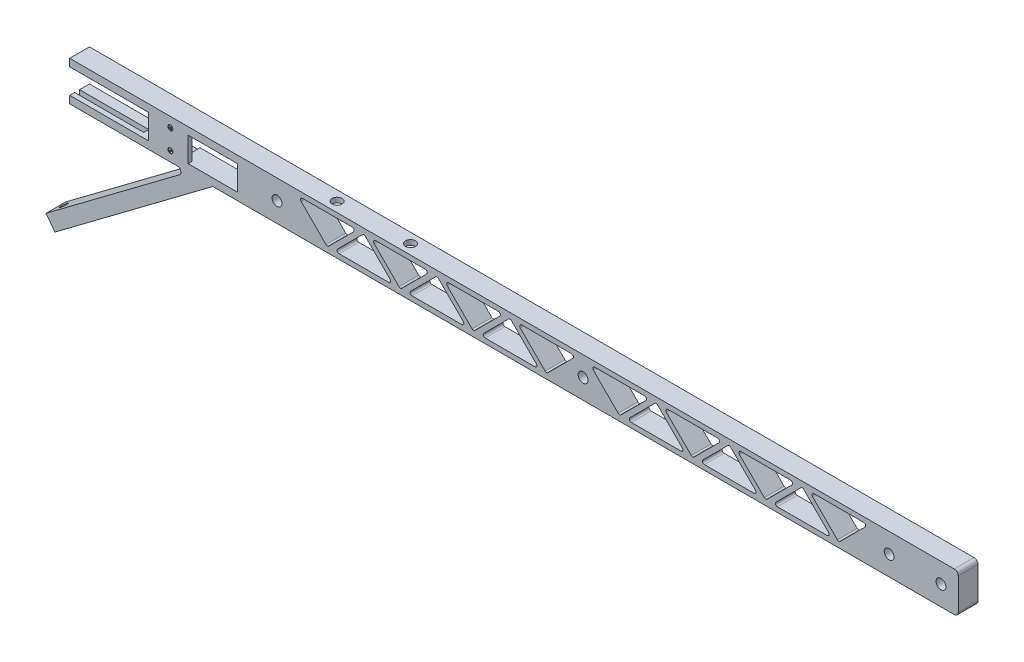
SolidWorks part; units mm, degrees
ref_plane "Front Plane" through (0, 0, 0) normal (0, 0, 1) x (1, 0, 0)
ref_plane "Top Plane" through (0, 0, 0) normal (0, 1, 0) x (1, 0, 0)
ref_plane "Right Plane" through (0, 0, 0) normal (1, 0, 0) x (0, 0, -1)
sketch "Sketch1" plane through (0, 0, 0) normal (0, 0, 1) x (1, 0, 0)
  line L0 (2.54, 0) -> (568.96, 0)
  line L1 (571.5, 2.54) -> (571.5, 22.86)
  line L2 (568.96, 25.4) -> (2.54, 25.4)
  line L3 (0, 22.86) -> (0, 2.54)
  line L4 (0, 22.86) -> (0, 25.4)
  line L5 (0, 25.4) -> (2.54, 25.4)
  line L6 (0, 2.54) -> (0, 0)
  line L7 (0, 0) -> (2.54, 0)
  arc A1 (568.96, 25.4) -> (571.5, 22.86) centre (568.96, 22.86) cw
  arc A2 (571.5, 2.54) -> (568.96, 0) centre (568.96, 2.54) cw
  point P7 (0, 25.4)
  point P12 (571.5, 0)
  point P15 (0, 0)
  dimension "D3" = 2.54
  dimension "D1" = 571.5
  dimension "D2" = 25.4
extrude "Boss-Extrude1" add sketch "Sketch1" along normal blind 12.7
sketch "Sketch2" plane through (0, 0, 0) normal (0, 0, 1) x (1, 0, 0)
  line L0 (173.2461, 3.175) -> (205.2139, 3.175)
  line L1 (206.112, 5.343) -> (190.128, 21.327)
  line L2 (188.332, 21.327) -> (172.348, 5.343)
  line L3 (0, 0) -> (568.96, 0) construction
  line L4 (0, 25.4) -> (0, 0) construction
  arc A0 (188.332, 21.327) -> (190.128, 21.327) centre (189.23, 20.4289) cw
  arc A1 (206.112, 5.343) -> (205.2139, 3.175) centre (205.2139, 4.445) cw
  arc A2 (173.2461, 3.175) -> (172.348, 5.343) centre (173.2461, 4.445) cw
  point P9 (189.23, 22.225)
  point P12 (208.28, 3.175)
  point P15 (170.18, 3.175)
  dimension "D5" = 1.27
  dimension "D1" = 38.1
  dimension "D2" = 19.05
  dimension "D3" = 3.175
  dimension "D4" = 170.18
extrude "Cut-Extrude1" cut sketch "Sketch2" along normal blind 12.7
pattern_linear "LPattern1" count 7 spacing 46.99 along (1, 0, 0) skipping (3, 0) of "Cut-Extrude1"
sketch "Sketch3" plane through (0, 0, 0) normal (0, 0, 1) x (1, 0, 0)
  line L0 (149.7511, 22.225) -> (181.7189, 22.225)
  line L1 (182.617, 20.057) -> (166.633, 4.073)
  line L2 (164.837, 4.073) -> (148.853, 20.057)
  line L3 (568.96, 25.4) -> (0, 25.4) construction
  line L4 (0, 25.4) -> (0, 0) construction
  arc A0 (164.837, 4.073) -> (166.633, 4.073) centre (165.735, 4.9711) ccw
  arc A1 (182.617, 20.057) -> (181.7189, 22.225) centre (181.7189, 20.955) ccw
  arc A2 (149.7511, 22.225) -> (148.853, 20.057) centre (149.7511, 20.955) ccw
  point P9 (165.735, 3.175)
  point P12 (184.785, 22.225)
  point P15 (146.685, 22.225)
  dimension "D5" = 1.27
  dimension "D1" = 38.1
  dimension "D2" = 19.05
  dimension "D3" = 3.175
  dimension "D4" = 146.685
extrude "Cut-Extrude2" cut sketch "Sketch3" along normal blind 12.7
pattern_linear "LPattern2" count 8 spacing 46.99 along (1, 0, 0) of "Cut-Extrude2"
ref_plane "Plane1" through (292.1, 0, 0) normal (1, 0, 0) x (0, 0, -1)
sketch "Sketch8" plane through (0, 0, 0) normal (0, 0, 1) x (1, 0, 0)
  line L0 (92.075, 0) -> (-9.525, -76.2)
  line L1 (0, 0) -> (568.96, 0) construction
  line L2 (-9.525, -76.2) -> (-15.24, -68.58)
  line L3 (-15.24, -68.58) -> (76.2, 0)
  line L4 (76.2, 0) -> (92.075, 0)
  line L5 (0, 25.4) -> (0, 0) construction
  dimension "D1" = 76.2
  dimension "D2" = 101.6
  dimension "D3" = 9.525
  dimension "D4" = 76.2
extrude "Boss-Extrude3" add sketch "Sketch8" along normal blind 12.7
hole_wizard "Ø5.0mm Dowel Hole1" positions "Sketch9" profile "Sketch10" hole size "Ø5.0" standard "ANSI Metric"
sketch "Sketch9" plane through (33.147, -44.196, 0) normal (0.6, -0.8, 0) x (-0.8, -0.6, 0)
  line L0 (53.34, -12.7) -> (53.34, 0) construction
  line L1 (53.34, 0) -> (-73.66, 0) construction
  point P0 (46.99, -6.35)
  dimension "D1" = 6.35
  dimension "D2" = 6.35
sketch "Sketch10" plane through (-4.445, -72.39, 6.35) normal (0, 0, 1) x (0.8, 0.6, 0)
  line L0 (0, 0) -> (0, 11.0272)
  line L1 (0, 11.0272) -> (2.5, 9.525)
  line L2 (2.5, 9.525) -> (2.5, 0)
  line L5 (2.5, 0) -> (0, 0)
  line L10 (0, 11.0272) -> (-2.5, 9.525) construction
  line L11 (0, -6.35) -> (0, 107.95) construction
  dimension "Hole Dia." = 5
  dimension "Hole Depth" = 9.525
  dimension "Drill Angle" = 118
thread "Thread1" pitch 0.8 method extrude profile "Thread Profile1" start angle 0, offset 0, length 8.8138, pitch 0.8, diameter 5
ref_plane "Plane2" through (-2.445, -70.89, 6.35) normal (0, 0, 1) x (0.8, 0.6, 0)
sketch "Thread Profile1" plane through (-2.445, -70.89, 6.35) normal (0, 0, 1) x (0.8, 0.6, 0)
  line L0 (0, 0) -> (0, 0.8) construction
  line L11 (0, 0) -> (0, 0.7)
  line L12 (0, 0.7) -> (-0.433, 0.45)
  line L13 (-0.433, 0.45) -> (-0.433, 0.25)
  line L15 (-0.433, 0.25) -> (0, 0)
  line L17 (-0.433, 0.35) -> (0, 0.35) construction
  point P2 (0, 0)
  dimension "Pitch" = 0.8
  dimension "Profile_Angle" = 60
  dimension "Profile_Land" = 0.2
  dimension "Profile_Height" = 0.433
sketch "Sketch14" plane through (0, 0, 0) normal (0, 0, -1) x (-1, 0, 0)
  line L0 (-571.5, 2.54) -> (-571.5, 22.86) construction
  line L1 (-92.075, 0) -> (-568.96, 0) construction
  circle A0 centre (-560.3875, 12.7) radius 3.175
  dimension "D1" = 6.35
  dimension "D2" = 11.1125
  dimension "D3" = 12.7
extrude "Cut-Extrude5" cut sketch "Sketch14" against normal through all
sketch "Sketch15" plane through (0, 0, 12.7) normal (0, 0, 1) x (1, 0, 0)
  line L0 (0, 20.6375) -> (50.8, 20.6375)
  line L1 (0, 25.4) -> (0, 0) construction
  line L2 (50.8, 20.6375) -> (50.8, 4.7625)
  line L3 (50.8, 4.7625) -> (0, 4.7625)
  line L4 (0, 4.7625) -> (0, 20.6375)
  line L5 (568.96, 25.4) -> (0, 25.4) construction
  dimension "D1" = 15.875
  dimension "D2" = 50.8
  dimension "D3" = 4.7625
extrude "Cut-Extrude6" cut sketch "Sketch15" against normal through all
sketch "Sketch16" plane through (0, 0, 0) normal (-1, 0, 0) x (0, 0, 1)
  line L0 (6.35, 23.8125) -> (9.525, 23.8125)
  line L1 (9.525, 23.8125) -> (9.525, 1.5875)
  line L2 (9.525, 1.5875) -> (6.35, 1.5875)
  line L3 (6.35, 1.5875) -> (6.35, 23.8125)
  line L7 (12.7, 0) -> (0, 0) construction
  line L8 (12.7, 25.4) -> (12.7, 20.6375) construction
  dimension "D1" = 3.175
  dimension "D2" = 3.175
  dimension "D3" = 22.225
  dimension "D4" = 1.5875
extrude "Cut-Extrude7" cut sketch "Sketch16" against normal blind 44.45
sketch "Sketch17" plane through (0, 0, 0) normal (0, 0, 1) x (1, 0, 0)
  line L0 (50.8, 20.6375) -> (54.61, 20.6375)
  line L1 (107.95, 20.6375) -> (107.95, 4.7625)
  line L2 (107.95, 4.7625) -> (71.12, 4.7625)
  line L3 (50.8, 4.7625) -> (50.8, 20.6375)
  line L4 (54.61, 20.6375) -> (55.88, 22.225)
  line L5 (55.88, 22.225) -> (71.12, 22.225)
  line L6 (71.12, 22.225) -> (71.12, 20.6375)
  line L7 (71.12, 4.7625) -> (71.12, 3.175)
  line L8 (71.12, 3.175) -> (55.88, 3.175)
  line L9 (55.88, 3.175) -> (54.61, 4.7625)
  line L10 (54.61, 4.7625) -> (50.8, 4.7625)
  line L11 (71.12, 20.6375) -> (107.95, 20.6375)
  point P13 (52.705, 20.6375)
  point P15 (52.705, 4.7625)
  dimension "D1" = 57.15
  dimension "D2" = 15.24
  dimension "D3" = 16.51
  dimension "D4" = 1.5875
  dimension "D5" = 1.5875
  dimension "D6" = 3.81
  dimension "D7" = 3.81
  dimension "D8" = 5.08
extrude "Cut-Extrude8" cut sketch "Sketch17" along normal blind 10.16
sketch "Sketch18" plane through (0, 0, 10.16) normal (0, 0, -1) x (-1, 0, 0)
  line L0 (-107.95, 4.7625) -> (-76.2, 4.7625)
  line L1 (-71.12, 4.7625) -> (-107.95, 4.7625) construction
  line L2 (-76.2, 4.7625) -> (-76.2, 20.6375)
  line L3 (-107.95, 20.6375) -> (-71.12, 20.6375) construction
  line L4 (-76.2, 20.6375) -> (-107.95, 20.6375)
  line L5 (-107.95, 20.6375) -> (-107.95, 4.7625)
  dimension "D1" = 31.75
extrude "Cut-Extrude9" cut sketch "Sketch18" against normal blind 2.54
hole_wizard "1/8 (0.125) Diameter Hole1" positions "Sketch19" profile "Sketch20" hole size "1/8" standard "ANSI Inch" end condition through all
sketch "Sketch19" plane through (0, 0, 10.16) normal (0, 0, -1) x (-1, 0, 0)
  line L0 (-76.2, 4.7625) -> (-76.2, 20.6375) construction
  line L1 (-71.12, 22.225) -> (-55.88, 22.225) construction
  line L2 (-55.88, 3.175) -> (-71.12, 3.175) construction
  point P0 (-64.77, 19.05)
  point P2 (-64.77, 6.35)
  dimension "D1" = 11.43
  dimension "D2" = 3.175
  dimension "D3" = 11.43
  dimension "D4" = 3.175
sketch "Sketch20" plane through (64.77, 19.05, 10.16) normal (1, 0, 0) x (0, 1, 0)
  line L0 (0, 0) -> (0, 2.54)
  line L1 (0, 2.54) -> (1.5875, 2.54)
  line L2 (1.5875, 2.54) -> (1.5875, 0)
  line L5 (1.5875, 0) -> (0, 0)
  line L11 (0, -6.35) -> (0, 107.95) construction
  dimension "Thru Hole Dia." = 3.175
  dimension "Thru Hole Depth" = 2.54
thread "Thread2" pitch 0.635 method extrude profile "Thread Profile2" start angle 0, offset 0, length 1.9812, pitch 0.635, diameter 3.175
ref_plane "Plane3" through (66.3575, 19.05, 10.16) normal (0, -1, 0) x (1, 0, 0)
sketch "Thread Profile2" plane through (66.3575, 19.05, 10.16) normal (0, -1, 0) x (1, 0, 0)
  line L0 (0, 0) -> (0, 0.635) construction
  line L11 (0, 0) -> (0, 0.5556)
  line L12 (0, 0.5556) -> (-0.3437, 0.3572)
  line L13 (-0.3437, 0.3572) -> (-0.3437, 0.1984)
  line L15 (-0.3437, 0.1984) -> (0, 0)
  line L17 (-0.3437, 0.2778) -> (0, 0.2778) construction
  point P2 (0, 0)
  dimension "Pitch" = 0.635
  dimension "Profile_Angle" = 60
  dimension "Profile_Land" = 0.1588
  dimension "Profile_Height" = 0.3437
thread "Thread3" pitch 0.635 method extrude profile "Thread Profile3" start angle 0, offset 0, length 1.9812, pitch 0.635, diameter 3.175
ref_plane "Plane4" through (66.3575, 6.35, 10.16) normal (0, -1, 0) x (1, 0, 0)
sketch "Thread Profile3" plane through (66.3575, 6.35, 10.16) normal (0, -1, 0) x (1, 0, 0)
  line L0 (0, 0) -> (0, 0.635) construction
  line L11 (0, 0) -> (0, 0.5556)
  line L12 (0, 0.5556) -> (-0.3437, 0.3572)
  line L13 (-0.3437, 0.3572) -> (-0.3437, 0.1984)
  line L15 (-0.3437, 0.1984) -> (0, 0)
  line L17 (-0.3437, 0.2778) -> (0, 0.2778) construction
  point P2 (0, 0)
  dimension "Pitch" = 0.635
  dimension "Profile_Angle" = 60
  dimension "Profile_Land" = 0.1588
  dimension "Profile_Height" = 0.3437
sketch "Sketch21" plane through (0, 0, 0) normal (0, 0, -1) x (-1, 0, 0)
  line L0 (-76.2, 0) -> (-69.85, 0)
  line L1 (0, 0) -> (-76.2, 0) construction
  line L3 (-76.2, 0) -> (15.24, -68.58) construction
  line L4 (-71.12, -3.81) -> (-76.2, 0)
  arc A0 (-71.12, -3.81) -> (-69.85, 0) centre (-69.0094, -2.3969) cw
  dimension "D1" = 2.54
  dimension "D2" = 6.35
extrude "Boss-Extrude4" add sketch "Sketch21" against normal blind 12.7
hole_wizard "1/4 (0.25) Diameter Hole1" positions "Sketch22" profile "Sketch23" hole size "1/4" standard "ANSI Inch" end condition through all
sketch "Sketch22" plane through (0, 0, 12.7) normal (0, 0, 1) x (1, 0, 0)
  line L0 (568.96, 25.4) -> (0, 25.4) construction
  line L1 (107.95, 20.6375) -> (107.95, 4.7625) construction
  point P0 (133.35, 12.7)
  point P2 (330.2, 12.7)
  point P4 (527.05, 12.7)
  dimension "D1" = 12.7
  dimension "D2" = 25.4
  dimension "D3" = 12.7
  dimension "D4" = 222.25
  dimension "D5" = 12.7
  dimension "D6" = 419.1
sketch "Sketch23" plane through (133.35, 12.7, 12.7) normal (1, 0, 0) x (0, -1, 0)
  line L0 (0, 0) -> (0, 12.7)
  line L1 (0, 12.7) -> (3.175, 12.7)
  line L2 (3.175, 12.7) -> (3.175, 0)
  line L5 (3.175, 0) -> (0, 0)
  line L11 (0, -6.35) -> (0, 107.95) construction
  dimension "Thru Hole Dia." = 6.35
  dimension "Thru Hole Depth" = 12.7
hole_wizard "1/4 (0.25) Diameter Hole2" positions "Sketch24" profile "Sketch25" hole size "1/4" standard "ANSI Inch"
sketch "Sketch24" plane through (0, 25.4, 0) normal (0, 1, 0) x (1, 0, 0)
  line L0 (568.96, 0) -> (0, 0) construction
  point P0 (165.6261, -6.35)
  point P2 (212.8339, -6.35)
  dimension "D1" = 6.35
  dimension "D2" = 6.35
  dimension "D3" = 15.875
  dimension "D4" = 15.875
sketch "Sketch25" plane through (165.6261, 25.4, 6.35) normal (1, 0, 0) x (0, 0, 1)
  line L0 (0, 0) -> (0, 5.0827)
  line L1 (0, 5.0827) -> (3.175, 3.175)
  line L2 (3.175, 3.175) -> (3.175, 0)
  line L5 (3.175, 0) -> (0, 0)
  line L10 (0, 5.0827) -> (-3.175, 3.175) construction
  line L11 (0, -6.35) -> (0, 107.95) construction
  dimension "Hole Dia." = 6.35
  dimension "Hole Depth" = 3.175
  dimension "Drill Angle" = 118
